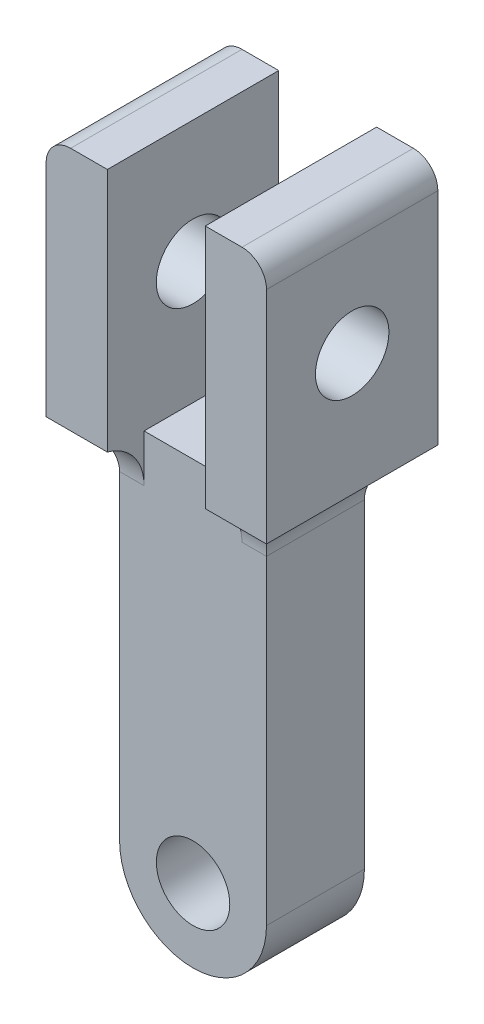
SolidWorks part; units mm, degrees
ref_plane "Front Plane" through (0, 0, 0) normal (0, 0, 1) x (1, 0, 0)
ref_plane "Top Plane" through (0, 0, 0) normal (0, 1, 0) x (1, 0, 0)
ref_plane "Right Plane" through (0, 0, 0) normal (1, 0, 0) x (0, 0, -1)
sketch "Sketch1" plane through (0, 0, 0) normal (0, 0, 1) x (1, 0, 0)
  line L0 (-3, 0) -> (-3, 15)
  line L1 (3, 0) -> (3, 15)
  line L3 (-3, 15) -> (3, 15)
  arc A0 (-3, 0) -> (3, 0) centre (0, 0) ccw
  circle A1 centre (0, 0) radius 1.5
  dimension "D1" = 6
  dimension "D2" = 3
  dimension "D3" = 15
  dimension "D4" = 15
extrude "Boss-Extrude1" add sketch "Sketch1" along normal blind 4
sketch "Sketch2" plane through (0, 15, 0) normal (0, 1, 0) x (1, 0, 0)
  line L1 (4.5, -5.5) -> (2, -5.5)
  line L2 (4.5, -5.5) -> (4.5, 1.5)
  line L3 (4.5, 1.5) -> (2, 1.5)
  line L4 (2, -5.5) -> (2, 1.5)
  line L10 (3, -4) -> (3, 0) construction
  line L11 (3, -4) -> (-3, -4) construction
  line L12 (3, 0) -> (-3, 0) construction
  dimension "D1" = 1
  dimension "D2" = 1.5
  dimension "D3" = 1.5
  dimension "D4" = 1.5
extrude "Boss-Extrude2" add sketch "Sketch2" along normal blind 10
mirror "Mirror3" about plane through (0, 0, 0) normal (1, 0, 0) of "Boss-Extrude2"
fillet "Fillet5" radius 2 3 edges at (-2.5, 15, 4) (-2.5, 15, 0) (-3, 15, 2)
fillet "Fillet6" radius 2 3 edges at (2.5, 15, 4) (2.5, 15, 0) (3, 15, 2)
sketch "Sketch3" plane through (-4.5, 0, 0) normal (-1, 0, 0) x (0, 0, 1)
  line L0 (5.5, 25) -> (-1.5, 25) construction
  line L1 (5.5, 25) -> (5.5, 15) construction
  circle A0 centre (2, 20) radius 1.5
  dimension "D3" = 3
  dimension "D1" = 5
  dimension "D2" = 3.5
extrude "Cut-Extrude1" cut sketch "Sketch3" against normal blind 10
fillet "Fillet8" radius 1 2 edges at (-4.5, 25, 2) (4.5, 25, 2)
